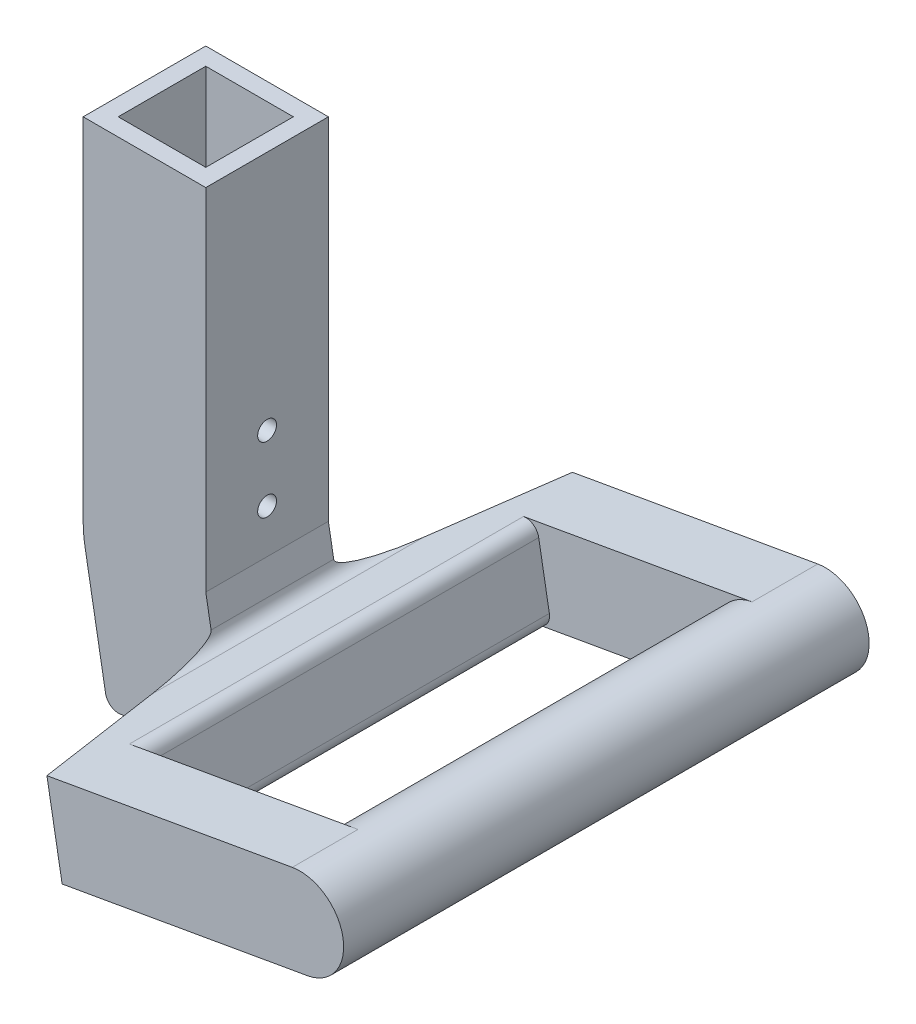
SolidWorks part; units mm, degrees
ref_plane "Front Plane" through (0, 0, 0) normal (0, 0, 1) x (1, 0, 0)
ref_plane "Top Plane" through (0, 0, 0) normal (0, 1, 0) x (1, 0, 0)
ref_plane "Right Plane" through (0, 0, 0) normal (1, 0, 0) x (0, 0, -1)
sketch "Sketch1" plane through (0, 0, 0) normal (0, 1, 0) x (1, 0, 0)
  line L0 (-4, 24) -> (24, 24)
  line L1 (0, 0) -> (20, 0)
  line L2 (0, 0) -> (0, 20)
  line L3 (0, 20) -> (20, 20)
  line L4 (20, 0) -> (20, 20)
  line L5 (24, -4) -> (24, 24)
  line L6 (-4, -4) -> (24, -4)
  line L7 (-4, -4) -> (-4, 24)
  dimension "D1" = 20
  dimension "D2" = 4
extrude "Boss-Extrude1" add sketch "Sketch1" along normal blind 30
sketch "Sketch2" plane through (0, 0, 0) normal (0, -1, 0) x (1, 0, 0)
  line L1 (-4, 4) -> (24, 4)
  line L2 (-4, 4) -> (-4, -24)
  line L3 (-4, -24) -> (24, -24)
  line L4 (24, 4) -> (24, -24)
extrude "Boss-Extrude2" add sketch "Sketch2" against normal blind 3
sketch "Sketch3" plane through (24, 0, 0) normal (1, 0, 0) x (0, 0, -1)
  line L0 (-4, 0) -> (24, 0) construction
  line L1 (-4, 30) -> (-4, 0) construction
  circle A0 centre (10, 25) radius 2.15
  circle A1 centre (10, 10) radius 2.15
  point P4 (0, 0)
  dimension "D1" = 4.3
  dimension "D2" = 15
  dimension "D3" = 10
  dimension "D4" = 14
extrude "Cut-Extrude1" cut sketch "Sketch3" against normal through all
sketch "Sketch4" plane through (0, 0, 4) normal (0, 0, 1) x (1, 0, 0)
  line L0 (24, 0) -> (29.2094, -29.5442)
  line L1 (29.2094, -29.5442) -> (1.6348, -34.4064)
  line L2 (1.6348, -34.4064) -> (-3.5746, -4.8621)
  line L3 (24, 30) -> (24, 0) construction
  line L4 (-4, 0) -> (24, 0) construction
  line L5 (-4, 0) -> (24, 0)
  arc A0 (-4, 0) -> (-3.5746, -4.8621) centre (24, 0) ccw
  dimension "D1" = 170
  dimension "D2" = 30
extrude "Boss-Extrude3" add sketch "Sketch4" against normal up to surface (28 mm away) up to face at (10, 15, -24)
sketch "Sketch5" plane through (5.9331, -33.6485, 0) normal (0.1736, -0.9848, 0) x (0, 0, -1)
  line L0 (24, 23.6354) -> (-4, 23.6354)
  line L1 (-4, 23.6354) -> (-50, 31.7464)
  line L2 (-50, 31.7464) -> (-50, 88.6354)
  line L3 (-50, 88.6354) -> (-35, 88.6354)
  line L4 (70, 88.6354) -> (70, 31.7464)
  line L5 (70, 31.7464) -> (24, 23.6354)
  line L6 (-35, 88.6354) -> (-35, 38.6354)
  line L7 (-35, 38.6354) -> (55, 38.6354)
  line L8 (55, 38.6354) -> (55, 88.6354)
  line L9 (55, 88.6354) -> (70, 88.6354)
  line L12 (-4, -4.3646) -> (-4, 23.6354) construction
  point P4 (-50, 35.3112)
  point P15 (55, 45.2172)
  dimension "D1" = 120
  dimension "D2" = 50
  dimension "D3" = 15
  dimension "D4" = 100
  dimension "D5" = 15
extrude "Boss-Extrude4" add sketch "Sketch5" against normal blind 20
sketch "Sketch6" plane through (0, 0, -55) normal (0, 0, 1) x (1, 0, 0)
  line L0 (89.749, 1.4391) -> (93.2219, -18.2571) construction
  circle A0 centre (91.4855, -8.409) radius 10
extrude "Boss-Extrude5" add sketch "Sketch6" along normal up to surface and the other way up to surface up to face at (63.4731, -13.3484, 50) other way up to face at (63.4731, -13.3484, -70)
sketch "Sketch7" plane through (0, 30, 0) normal (0, 1, 0) x (1, 0, 0)
  line L0 (20, 0) -> (20, 20) construction
  line L1 (0, 0) -> (20, 0) construction
  line L2 (0, 20) -> (0, 0) construction
  line L3 (20, 20) -> (0, 20) construction
  line L4 (-4, 24) -> (-4, -4)
  line L5 (-4, -4) -> (24, -4)
  line L6 (24, -4) -> (24, 24)
  line L7 (24, 24) -> (-4, 24)
  line L8 (-4, 24) -> (-4, -4)
  line L9 (-4, -4) -> (24, -4)
  line L10 (24, -4) -> (24, 24)
  line L11 (24, 24) -> (-4, 24)
  line L12 (20, 0) -> (20, 20)
  line L13 (0, 0) -> (20, 0)
  line L14 (0, 20) -> (0, 0)
  line L15 (20, 20) -> (0, 20)
  dimension "D1" = 0
extrude "Boss-Extrude6" add sketch "Sketch7" along normal blind 50
fillet "Fillet1" radius 3 4 edges at (43.9816, -26.9395, -10) (40.5086, -7.2434, -10) (25.7365, -9.8481, -10) (1.6348, -34.4064, -10)
